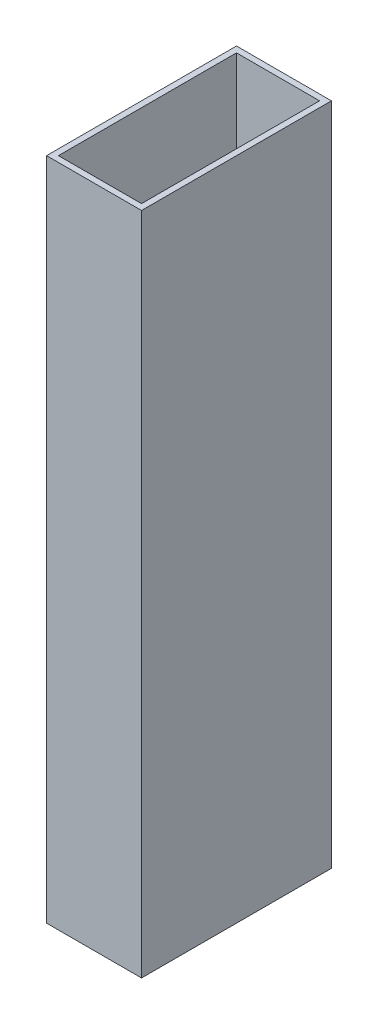
SolidWorks part; units mm, degrees
material "6061-T6 (SS)"
ref_plane "Front" through (0, 0, 0) normal (0, 0, 1) x (1, 0, 0)
ref_plane "Top" through (0, 0, 0) normal (0, 1, 0) x (1, 0, 0)
ref_plane "Right" through (0, 0, 0) normal (1, 0, 0) x (0, 0, -1)
sketch "Sketch1" plane through (0, 0, 0) normal (0, 1, 0) x (1, 0, 0)
  line L1 (12.7, 25.4) -> (-12.7, 25.4)
  line L2 (12.7, 25.4) -> (12.7, -25.4)
  line L3 (12.7, -25.4) -> (-12.7, -25.4)
  line L4 (-12.7, 25.4) -> (-12.7, -25.4)
  line L5 (12.7, 25.4) -> (-12.7, -25.4) construction
  line L6 (12.7, -25.4) -> (-12.7, 25.4) construction
  point P0 (0, 0)
  dimension "D1" = 25.4
  dimension "D2" = 50.8
extrude "Extrude-Thin1" add sketch "Sketch1" along normal blind 177.8 thin thin type one direction reverse wall 1.5875
